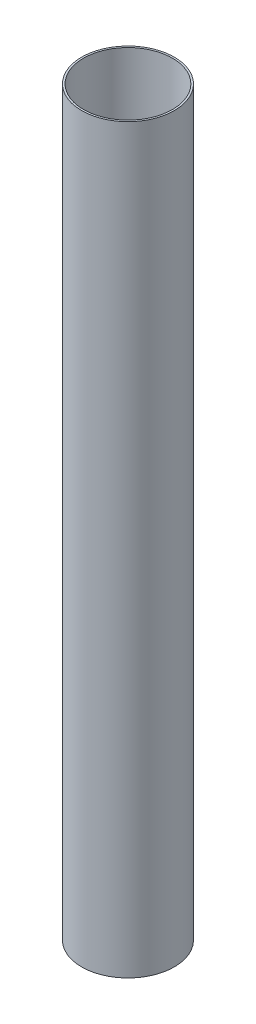
SolidWorks part; units mm, degrees
material "PC High Viscosity"
ref_plane "Front Plane" through (0, 0, 0) normal (0, 0, 1) x (1, 0, 0)
ref_plane "Top Plane" through (0, 0, 0) normal (0, 1, 0) x (1, 0, 0)
ref_plane "Right Plane" through (0, 0, 0) normal (1, 0, 0) x (0, 0, -1)
ref_axis "CentralAxis" through (0, 110, 0) along (0, -1, 0)
sketch "ProfileS" plane through (0, 0, 0) normal (0, 0, 1) x (1, 0, 0)
  line L0 (0, 100) -> (0, -100) construction
  line L1 (-12.5, 100) -> (-12.5, -100)
  line L2 (0, 0) -> (-12.5, 0) construction
  dimension "Height" = 200
  dimension "OuterDiameter" = 25
revolve "Profile" add sketch "ProfileS" angle 360 about L0 wall 0.5
